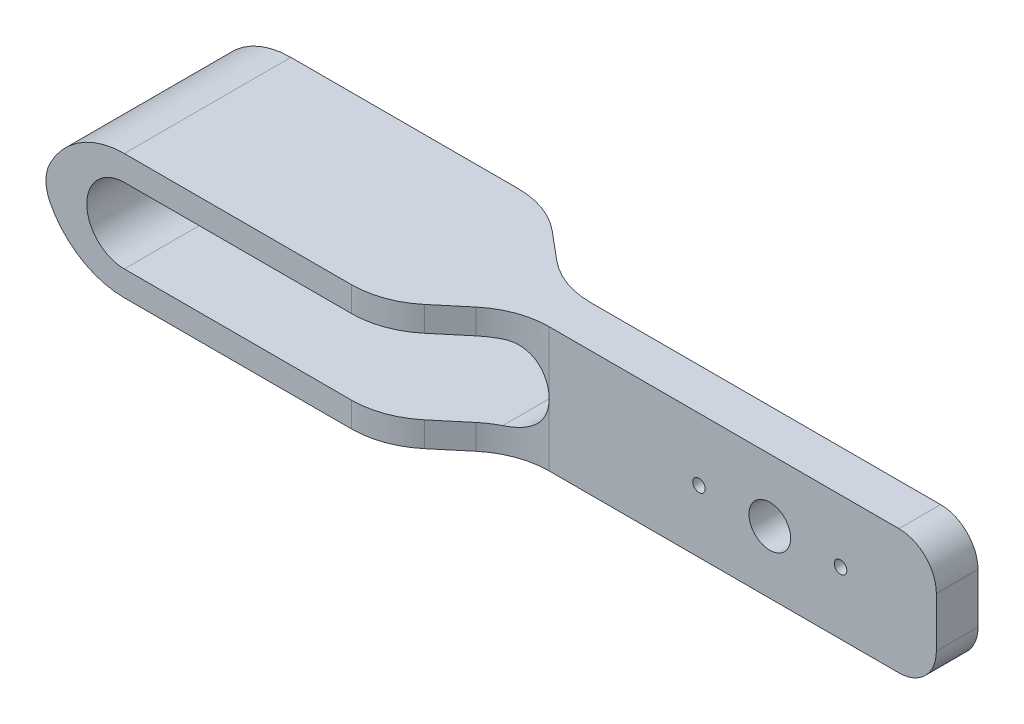
SolidWorks part; units mm, degrees
ref_plane "Plano frontal" through (0, 0, 0) normal (0, 0, 1) x (1, 0, 0)
ref_plane "Plano superior" through (0, 0, 0) normal (0, 1, 0) x (1, 0, 0)
ref_plane "Plano direito" through (0, 0, 0) normal (1, 0, 0) x (0, 0, -1)
sketch "Esboço1" plane through (0, 0, 0) normal (0, 0, 1) x (1, 0, 0)
  line L13 (-17.5, -6) -> (22.5, -6)
  line L14 (-17.5, -6) -> (-17.5, 9)
  line L15 (-17.5, 9) -> (22.5, 9)
  line L16 (22.5, -6) -> (22.5, 9)
  dimension "D3" = 15
  dimension "D4" = 40
extrude "Ressalto-extrusão1" add sketch "Esboço1" against normal blind 3 contours L13 L16 L15 L14 region at (2.5, 1.5, 0)
sketch "Esboço2" plane through (0, 0, 0) normal (0, 0, 1) x (1, 0, 0)
  line L0 (-17.5, 9) -> (22.5, -6) construction
  line L7 (-17.5, -6) -> (22.5, 9) construction
  circle A0 centre (2.5, 1.5) radius 2.5
  circle A4 centre (-6, 1.5) radius 0.75
  dimension "D1" = 1.5
  dimension "D3" = 5
  dimension "D2" = 8.5
sketch "Esboço3" plane through (0, 0, 0) normal (0, 0, 1) x (1, 0, 0)
  line L1 (-17.5, -6) -> (22.5, -6)
  line L2 (-17.5, -6) -> (-17.5, 9)
  line L3 (-17.5, 9) -> (22.5, 9)
  line L4 (22.5, -6) -> (22.5, 9)
extrude "Ressalto-extrusão2" add sketch "Esboço3" along normal blind 2
extrude "Corte-extrusão1" cut sketch "Esboço2" along normal up to surface and the other way up to surface up to face at (2.5, 1.5, 2) other way up to face at (2.5, 1.5, -3)
sketch "Esboço4" plane through (0, 9, 0) normal (0, 1, 0) x (1, 0, 0)
  line L0 (22.5, -2) -> (-17.5, -2) construction
  line L1 (6.2, -34.5) -> (-6.2, -34.5)
  line L2 (6.2, -34.5) -> (6.2, -11.5)
  line L3 (6.2, -11.5) -> (-6.2, -11.5)
  line L4 (-6.2, -34.5) -> (-6.2, -11.5)
  line L5 (-17.5, 3) -> (22.5, 3) construction
  line L6 (17.5, -2) -> (-12.5, -2)
  line L7 (17.5, -2) -> (17.5, -42)
  line L8 (17.5, -42) -> (-12.5, -42)
  line L9 (-12.5, -2) -> (-12.5, -42)
  line L10 (-12.5, -2) -> (17.5, -2)
  line L11 (-12.5, -2) -> (-12.5, 3)
  line L12 (-12.5, 3) -> (17.5, 3)
  line L13 (17.5, -2) -> (17.5, 3)
  circle A0 centre (0, -9.75) radius 1.25
  circle A1 centre (0, -36.25) radius 1.25
  point P6 (0, -34.5)
  point P13 (2.5, -2)
  point P14 (2.5, -42)
  line M5 (-17.5, -2) -> (22.5, -2)
  line M7 (22.5, 3) -> (-17.5, 3)
  dimension "D6" = 7.75
  dimension "D7" = 2.5
  dimension "D8" = 26.5
  dimension "D1" = 9.5
  dimension "D2" = 23
  dimension "D3" = 12.4
  dimension "D4" = 30
  dimension "D5" = 40
extrude "Ressalto-extrusão3" [suppressed] add sketch "Esboço4" against normal blind 3 contours L13 L11 M5 M7 | L9 L8 L7 L1 L4 L3 L2 M5
fillet "Filete2" [suppressed] radius 5
fillet "Filete3" [suppressed] radius 10
sketch "Esboço5" plane through (-17.5, 0, 0) normal (-1, 0, 0) x (0, 0, 1)
  line L0 (-3, 9) -> (2, 9) construction
  line L1 (-10.5, -6) -> (9.5, -6)
  line L2 (-10.5, -6) -> (-10.5, 9)
  line L3 (-10.5, 9) -> (9.5, 9)
  line L4 (9.5, -6) -> (9.5, 9)
  line L5 (-3, -6) -> (2, -6) construction
  point P13 (-0.5, -6)
  point P14 (-0.5, -6)
  dimension "D1" = 20
extrude "Ressalto-extrusão4" add sketch "Esboço5" along normal blind 60
chamfer "Chanfro1" distance 16 angle 50 2 edges at (-17.5, 1.5, 9.5) (-17.5, 1.5, -10.5) first distance on face at (-17.5, 1.5, 5.75) first distance on face at (-17.5, 1.5, -6.75)
fillet "Filete4" radius 10 6 edges at (-36.5681, 1.5, 9.5) (-27.6299, 1.5, 2) (-77.5, 9, -0.5) (-77.5, -6, -0.5) (-36.5681, 1.5, -10.5) (-27.6299, 1.5, -3)
sketch "Esboço6" plane through (0, 0, 9.5) normal (0, 0, 1) x (1, 0, 0)
  line L0 (-43.2078, 6) -> (-67.5, 6)
  line L1 (-67.5, -3) -> (-43.2078, -3)
  line L2 (-43.2078, -3) -> (-43.2078, 6) construction
  line L3 (-40.2078, 9) -> (-67.5, 9)
  line L4 (-67.5, -6) -> (-40.2078, -6)
  line L5 (-40.2078, -6) -> (-40.2078, 9)
  line L6 (-40.2078, 9) -> (-67.5, 9) construction
  line L7 (-67.5, -6) -> (-40.2078, -6) construction
  line L8 (-40.2078, -6) -> (-40.2078, 9) construction
  line L9 (-43.2078, 6) -> (-23.9902, 6)
  line L10 (-23.9902, 9) -> (-23.9902, -6) construction
  line L11 (-43.2078, -3) -> (-23.9902, -3)
  line L12 (-23.9902, -3) -> (-23.9902, 6)
  arc A0 (-67.5, 6) -> (-74.0383, 1.5) centre (-67.5, -1) ccw
  arc A1 (-74.0383, 1.5) -> (-67.5, -3) centre (-67.5, 4) ccw
  arc A2 (-67.5, 9) -> (-77.1825, 1.5) centre (-67.5, -1) ccw
  arc A3 (-77.1825, 1.5) -> (-67.5, -6) centre (-67.5, 4) ccw
  arc A4 (-67.5, 9) -> (-77.1825, 1.5) centre (-67.5, -1) ccw construction
  arc A5 (-77.1825, 1.5) -> (-67.5, -6) centre (-67.5, 4) ccw construction
  dimension "D1" = 0
  dimension "D2" = 3
extrude "Corte-extrusão2" cut sketch "Esboço6" against normal through all
fillet "Filete5" radius 4.5 4 edges at (-23.9902, -3, -0.5) (-23.9902, 6, -0.5) (22.5, -6, -0.5) (22.5, 9, -0.5)
pattern_circular "CirPattern1" count 2 over 360 about axis through (2.5, 1.5, 2) along (0, 0, -1) of "Corte-extrusão1"
fillet "Fillet1" radius 4.5 2 edges at (-77.1825, 1.5, -0.5) (-74.0383, 1.5, -0.5)
